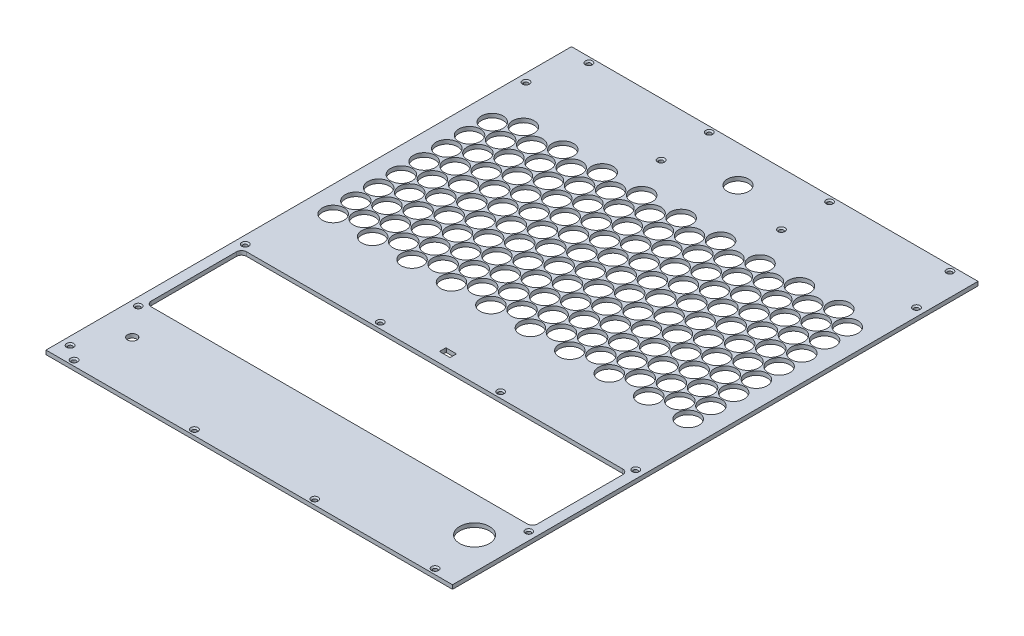
SolidWorks part; units mm, degrees
ref_plane "Ebene vorne" through (0, 0, 0) normal (0, 0, 1) x (1, 0, 0)
ref_plane "Ebene oben" through (0, 0, 0) normal (0, 1, 0) x (1, 0, 0)
ref_plane "Ebene rechts" through (0, 0, 0) normal (1, 0, 0) x (0, 0, -1)
sketch "Skizze1" plane through (0, 0, 0) normal (0, 1, 0) x (1, 0, 0)
  line L1 (-152, 250) -> (152, 250)
  line L2 (-152, 250) -> (-152, -143)
  line L3 (-152, -143) -> (152, -143)
  line L4 (152, 250) -> (152, -143)
  line L5 (-152, 250) -> (152, -143) construction
  line L6 (-152, -143) -> (152, 250) construction
  point P0 (0, 53.5)
extrude "Aufsatz-Linear austragen1" add sketch "Skizze1" along normal blind 3
sketch "Skizze3" plane through (0, 3, 0) normal (0, 1, 0) x (1, 0, 0)
  line L0 (0, 0) -> (0, 250)
  line L1 (152, 250) -> (-152, 250) construction
  circle A0 centre (-146, -131) radius 1.6
  circle A1 centre (-146, -80) radius 1.6
  circle A2 centre (-146, 0) radius 1.6
  circle A3 centre (-146, 210) radius 1.6
  circle A4 centre (-45, 0) radius 1.6
  circle A5 centre (-45, 210) radius 1.6
  circle A6 centre (45, 210) radius 1.6
  circle A7 centre (45, 0) radius 1.6
  circle A8 centre (146, 210) radius 1.6
  circle A9 centre (146, 0) radius 1.6
  circle A10 centre (146, -80) radius 1.6
extrude "PCB-Screws" cut sketch "Skizze3" against normal through all contours A0 | A1 | A2 | A4 | A7 | A9 | A10 | A8 | A6 | A5 | A3 region at (-146, 3, 131) region at (-146, 3, 80) region at (-146, 3, 0) region at (-146, 3, -210) region at (-45, 3, 0) region at (-45, 3, -210) region at (45, 3, -210) region at (45, 3, 0) region at (146, 3, -210) region at (146, 3, 0) region at (146, 3, 80)
sketch "Skizze4" plane through (0, 3, 0) normal (0, 1, 0) x (1, 0, 0)
  circle A0 centre (0, 61) radius 8.075
  circle A1 centre (0, 78) radius 8.075
  circle A2 centre (0, 95) radius 8.075
  circle A3 centre (0, 112) radius 8.075
  circle A4 centre (0, 129) radius 8.075
  circle A5 centre (0, 146) radius 8.075
  circle A6 centre (0, 163) radius 8.075
  circle A7 centre (0, 180) radius 8.075
  circle A8 centre (-14.75, 52.5) radius 8.075
  circle A9 centre (-14.75, 69.5) radius 8.075
  circle A10 centre (-14.75, 86.5) radius 8.075
  circle A11 centre (-14.75, 103.5) radius 8.075
  circle A12 centre (-14.75, 120.5) radius 8.075
  circle A13 centre (-14.75, 137.5) radius 8.075
  circle A14 centre (-14.75, 154.5) radius 8.075
  circle A15 centre (-14.75, 171.5) radius 8.075
  circle A16 centre (-29.5, 61) radius 8.075
  circle A17 centre (-29.5, 78) radius 8.075
  circle A18 centre (-29.5, 95) radius 8.075
  circle A19 centre (-29.5, 112) radius 8.075
  circle A20 centre (-29.5, 129) radius 8.075
  circle A21 centre (-29.5, 146) radius 8.075
  circle A22 centre (-29.5, 163) radius 8.075
  circle A23 centre (-29.5, 180) radius 8.075
  circle A24 centre (-44.25, 52.5) radius 8.075
  circle A25 centre (-44.25, 69.5) radius 8.075
  circle A26 centre (-44.25, 86.5) radius 8.075
  circle A27 centre (-44.25, 103.5) radius 8.075
  circle A28 centre (-44.25, 120.5) radius 8.075
  circle A29 centre (-44.25, 137.5) radius 8.075
  circle A30 centre (-44.25, 154.5) radius 8.075
  circle A31 centre (-44.25, 171.5) radius 8.075
  circle A32 centre (-59, 61) radius 8.075
  circle A33 centre (-59, 78) radius 8.075
  circle A34 centre (-59, 95) radius 8.075
  circle A35 centre (-59, 112) radius 8.075
  circle A36 centre (-59, 129) radius 8.075
  circle A37 centre (-59, 146) radius 8.075
  circle A38 centre (-59, 163) radius 8.075
  circle A39 centre (-59, 180) radius 8.075
  circle A40 centre (-73.75, 52.5) radius 8.075
  circle A41 centre (-73.75, 69.5) radius 8.075
  circle A42 centre (-73.75, 86.5) radius 8.075
  circle A43 centre (-73.75, 103.5) radius 8.075
  circle A44 centre (-73.75, 120.5) radius 8.075
  circle A45 centre (-73.75, 137.5) radius 8.075
  circle A46 centre (-73.75, 154.5) radius 8.075
  circle A47 centre (-73.75, 171.5) radius 8.075
  circle A48 centre (-88.5, 61) radius 8.075
  circle A49 centre (-88.5, 78) radius 8.075
  circle A50 centre (-88.5, 95) radius 8.075
  circle A51 centre (-88.5, 112) radius 8.075
  circle A52 centre (-88.5, 129) radius 8.075
  circle A53 centre (-88.5, 146) radius 8.075
  circle A54 centre (-88.5, 163) radius 8.075
  circle A55 centre (-88.5, 180) radius 8.075
  circle A56 centre (-103.25, 52.5) radius 8.075
  circle A57 centre (-103.25, 69.5) radius 8.075
  circle A58 centre (-103.25, 86.5) radius 8.075
  circle A59 centre (-103.25, 103.5) radius 8.075
  circle A60 centre (-103.25, 120.5) radius 8.075
  circle A61 centre (-103.25, 137.5) radius 8.075
  circle A62 centre (-103.25, 154.5) radius 8.075
  circle A63 centre (-103.25, 171.5) radius 8.075
  circle A64 centre (-118, 61) radius 8.075
  circle A65 centre (-118, 78) radius 8.075
  circle A66 centre (-118, 95) radius 8.075
  circle A67 centre (-118, 112) radius 8.075
  circle A68 centre (-118, 129) radius 8.075
  circle A69 centre (-118, 146) radius 8.075
  circle A70 centre (-118, 163) radius 8.075
  circle A71 centre (-118, 180) radius 8.075
  circle A72 centre (-132.75, 52.5) radius 8.075
  circle A73 centre (-132.75, 69.5) radius 8.075
  circle A74 centre (-132.75, 86.5) radius 8.075
  circle A75 centre (-132.75, 103.5) radius 8.075
  circle A76 centre (-132.75, 120.5) radius 8.075
  circle A77 centre (-132.75, 137.5) radius 8.075
  circle A78 centre (-132.75, 154.5) radius 8.075
  circle A79 centre (-132.75, 171.5) radius 8.075
  circle A80 centre (29.5, 61) radius 8.075
  circle A81 centre (29.5, 78) radius 8.075
  circle A82 centre (29.5, 95) radius 8.075
  circle A83 centre (29.5, 112) radius 8.075
  circle A84 centre (29.5, 129) radius 8.075
  circle A85 centre (29.5, 146) radius 8.075
  circle A86 centre (29.5, 163) radius 8.075
  circle A87 centre (29.5, 180) radius 8.075
  circle A88 centre (14.75, 52.5) radius 8.075
  circle A89 centre (14.75, 69.5) radius 8.075
  circle A90 centre (14.75, 86.5) radius 8.075
  circle A91 centre (14.75, 103.5) radius 8.075
  circle A92 centre (14.75, 120.5) radius 8.075
  circle A93 centre (14.75, 137.5) radius 8.075
  circle A94 centre (14.75, 154.5) radius 8.075
  circle A95 centre (14.75, 171.5) radius 8.075
  circle A96 centre (59, 61) radius 8.075
  circle A97 centre (59, 78) radius 8.075
  circle A98 centre (59, 95) radius 8.075
  circle A99 centre (59, 112) radius 8.075
  circle A100 centre (59, 129) radius 8.075
  circle A101 centre (59, 146) radius 8.075
  circle A102 centre (59, 163) radius 8.075
  circle A103 centre (59, 180) radius 8.075
  circle A104 centre (44.25, 52.5) radius 8.075
  circle A105 centre (44.25, 69.5) radius 8.075
  circle A106 centre (44.25, 86.5) radius 8.075
  circle A107 centre (44.25, 103.5) radius 8.075
  circle A108 centre (44.25, 120.5) radius 8.075
  circle A109 centre (44.25, 137.5) radius 8.075
  circle A110 centre (44.25, 154.5) radius 8.075
  circle A111 centre (44.25, 171.5) radius 8.075
  circle A112 centre (88.5, 61) radius 8.075
  circle A113 centre (88.5, 78) radius 8.075
  circle A114 centre (88.5, 95) radius 8.075
  circle A115 centre (88.5, 112) radius 8.075
  circle A116 centre (88.5, 129) radius 8.075
  circle A117 centre (88.5, 146) radius 8.075
  circle A118 centre (88.5, 163) radius 8.075
  circle A119 centre (88.5, 180) radius 8.075
  circle A120 centre (73.75, 52.5) radius 8.075
  circle A121 centre (73.75, 69.5) radius 8.075
  circle A122 centre (73.75, 86.5) radius 8.075
  circle A123 centre (73.75, 103.5) radius 8.075
  circle A124 centre (73.75, 120.5) radius 8.075
  circle A125 centre (73.75, 137.5) radius 8.075
  circle A126 centre (73.75, 154.5) radius 8.075
  circle A127 centre (73.75, 171.5) radius 8.075
  circle A128 centre (118, 61) radius 8.075
  circle A129 centre (118, 78) radius 8.075
  circle A130 centre (118, 95) radius 8.075
  circle A131 centre (118, 112) radius 8.075
  circle A132 centre (118, 129) radius 8.075
  circle A133 centre (118, 146) radius 8.075
  circle A134 centre (118, 163) radius 8.075
  circle A135 centre (118, 180) radius 8.075
  circle A136 centre (103.25, 52.5) radius 8.075
  circle A137 centre (103.25, 69.5) radius 8.075
  circle A138 centre (103.25, 86.5) radius 8.075
  circle A139 centre (103.25, 103.5) radius 8.075
  circle A140 centre (103.25, 120.5) radius 8.075
  circle A141 centre (103.25, 137.5) radius 8.075
  circle A142 centre (103.25, 154.5) radius 8.075
  circle A143 centre (103.25, 171.5) radius 8.075
  circle A152 centre (132.75, 52.5) radius 8.075
  circle A153 centre (132.75, 69.5) radius 8.075
  circle A154 centre (132.75, 86.5) radius 8.075
  circle A155 centre (132.75, 103.5) radius 8.075
  circle A156 centre (132.75, 120.5) radius 8.075
  circle A157 centre (132.75, 137.5) radius 8.075
  circle A158 centre (132.75, 154.5) radius 8.075
  circle A159 centre (132.75, 171.5) radius 8.075
  circle A160 centre (147.5, 61) radius 8.075 [skipped]
  circle A161 centre (147.5, 78) radius 8.075 [skipped]
  circle A162 centre (147.5, 95) radius 8.075 [skipped]
  circle A163 centre (147.5, 112) radius 8.075 [skipped]
  circle A164 centre (147.5, 129) radius 8.075 [skipped]
  circle A165 centre (147.5, 146) radius 8.075 [skipped]
  circle A166 centre (147.5, 163) radius 8.075 [skipped]
  circle A167 centre (147.5, 180) radius 8.075 [skipped]
  dimension "D1" = 8
  dimension "D2" = 8
extrude "Transducers" cut sketch "Skizze4" against normal through all
sketch "Skizze5" plane through (0, 3, 0) normal (0, 1, 0) x (1, 0, 0)
  line L0 (-3.45, 8.02) -> (3.45, 8.02)
  line L1 (-3.2, 7.27) -> (3.2, 7.27)
  line L2 (-3.2, 7.27) -> (-3.2, 3.97)
  line L3 (-3.2, 3.97) -> (3.2, 3.97)
  line L4 (3.2, 7.27) -> (3.2, 3.97)
  line L5 (-3.2, 7.27) -> (3.2, 3.97) construction
  line L6 (-3.2, 3.97) -> (3.2, 7.27) construction
  line L7 (3.95, 7.52) -> (3.95, 3.72)
  line L8 (-3.45, 3.22) -> (3.45, 3.22)
  line L9 (-3.95, 7.52) -> (-3.95, 3.72)
  line L10 (-3.95, 8.02) -> (3.95, 8.02) construction
  line L11 (3.95, 8.02) -> (3.95, 3.22) construction
  line L12 (-3.95, 3.22) -> (3.95, 3.22) construction
  line L13 (-3.95, 8.02) -> (-3.95, 3.22) construction
  arc A0 (3.45, 8.02) -> (3.95, 7.52) centre (3.45, 7.52) cw
  arc A1 (3.95, 3.72) -> (3.45, 3.22) centre (3.45, 3.72) cw
  arc A2 (-3.45, 3.22) -> (-3.95, 3.72) centre (-3.45, 3.72) cw
  arc A3 (-3.45, 8.02) -> (-3.95, 7.52) centre (-3.45, 7.52) ccw
  point P0 (0, 5.62)
  dimension "D2" = 0.5
  dimension "D1" = 0.75
extrude "ToF-Sensor" cut sketch "Skizze5" against normal through all contours L0 A3 L9 A2 L8 A1 L7 A0 L1 L4 L3 L2 | L4 L1 L2 L3 region at (0, 3, -7.9276) region at (0, 3, -5.62)
sketch "Skizze6" plane through (0, 3, 0) normal (0, 1, 0) x (1, 0, 0)
  line L0 (-144.4, -8.1) -> (-144.4, -71.9)
  line L1 (-140.65, -5.1) -> (140.65, -5.1)
  line L2 (-143.65, -8.1) -> (-143.65, -71.9)
  line L3 (-140.65, -74.9) -> (140.65, -74.9)
  line L4 (143.65, -8.1) -> (143.65, -71.9)
  line L5 (-143.65, -5.1) -> (143.65, -74.9) construction
  line L6 (-143.65, -74.9) -> (143.65, -5.1) construction
  line L7 (-140.65, -75.65) -> (140.65, -75.65)
  line L8 (144.4, -8.1) -> (144.4, -71.9)
  line L9 (-140.65, -4.35) -> (140.65, -4.35)
  arc A0 (140.65, -74.9) -> (143.65, -71.9) centre (140.65, -71.9) ccw
  arc A1 (-143.65, -71.9) -> (-140.65, -74.9) centre (-140.65, -71.9) ccw
  arc A2 (-140.65, -5.1) -> (-143.65, -8.1) centre (-140.65, -8.1) ccw
  arc A3 (140.65, -5.1) -> (143.65, -8.1) centre (140.65, -8.1) cw
  arc A4 (-144.4, -71.9) -> (-140.65, -75.65) centre (-140.65, -71.9) ccw
  arc A5 (140.65, -75.65) -> (144.4, -71.9) centre (140.65, -71.9) ccw
  arc A6 (140.65, -4.35) -> (144.4, -8.1) centre (140.65, -8.1) cw
  arc A7 (-140.65, -4.35) -> (-144.4, -8.1) centre (-140.65, -8.1) ccw
  point P0 (0, -40)
  dimension "D1" = 3
  dimension "D2" = 0.75
extrude "Display" cut sketch "Skizze6" against normal through all contours L9 A7 L0 A4 L7 A5 L8 A6 L1 A3 L4 A0 L3 A1 L2 A2 | A3 L1 A2 L2 A1 L3 A0 L4 region at (-143.0913, 3, 5.6587) region at (0, 3, 40)
sketch "Skizze7" plane through (0, 3, 0) normal (0, 1, 0) x (1, 0, 0)
  circle A0 centre (0, 222.5) radius 8
extrude "Camera" cut sketch "Skizze7" against normal through all
sketch "Skizze9" plane through (0, 3, 0) normal (0, 1, 0) x (1, 0, 0)
  circle A0 centre (-128, -102.5) radius 3.5
extrude "Rotary Encoder" cut sketch "Skizze9" against normal through all
sketch "Skizze10" plane through (0, 3, 0) normal (0, 1, 0) x (1, 0, 0)
  circle A0 centre (128, -102.5) radius 11.1
extrude "RGB-Button" cut sketch "Skizze10" against normal through all
sketch "Skizze8" plane through (0, 3, 0) normal (0, 1, 0) x (1, 0, 0)
  line L0 (152, -143) -> (152, 250) construction
  line L1 (-152, -143) -> (152, -143)
  line L2 (-152, -143) -> (-152, -135)
  line L3 (-152, -135) -> (152, -135)
  line L5 (-152, 53.5) -> (152, 53.5)
  line L10 (-152, 250) -> (-152, -143) construction
  line L11 (0, -135) -> (0, -143)
  circle A0 centre (-135, -139) radius 1.6
  circle A2 centre (-45, -139) radius 1.6
  circle A3 centre (45, -139) radius 1.6
  circle A4 centre (135, -139) radius 1.6
  circle A5 centre (135, 246) radius 1.6
  circle A6 centre (45, 246) radius 1.6
  circle A7 centre (-45, 246) radius 1.6
  circle A8 centre (-135, 246) radius 1.6
extrude "Main-Screws" cut sketch "Skizze8" against normal through all contours A8 | A7 | A6 | A5 | A0 | A2 | A3 | A4 region at (-135, 3, 139) region at (-45, 3, 139) region at (45, 3, 139) region at (135, 3, 139) region at (135, 3, -246) region at (45, 3, -246) region at (-45, 3, -246) region at (-135, 3, -246)
chamfer "Fase1" distance 1 angle 45 19 edges at (135, 3, -244.4) (146, 3, -208.4) (45, 3, -244.4) (45, 3, -208.4) (-45, 3, -244.4) (-45, 3, -208.4) (-135, 3, -244.4) (-146, 3, -208.4) (146, 3, 1.6) (45, 3, 1.6) (-45, 3, 1.6) (-146, 3, 1.6) (146, 3, 81.6) (135, 3, 140.6) (45, 3, 140.6) (-45, 3, 140.6) (-146, 3, 81.6) (-135, 3, 140.6) (-146, 3, 132.6)
